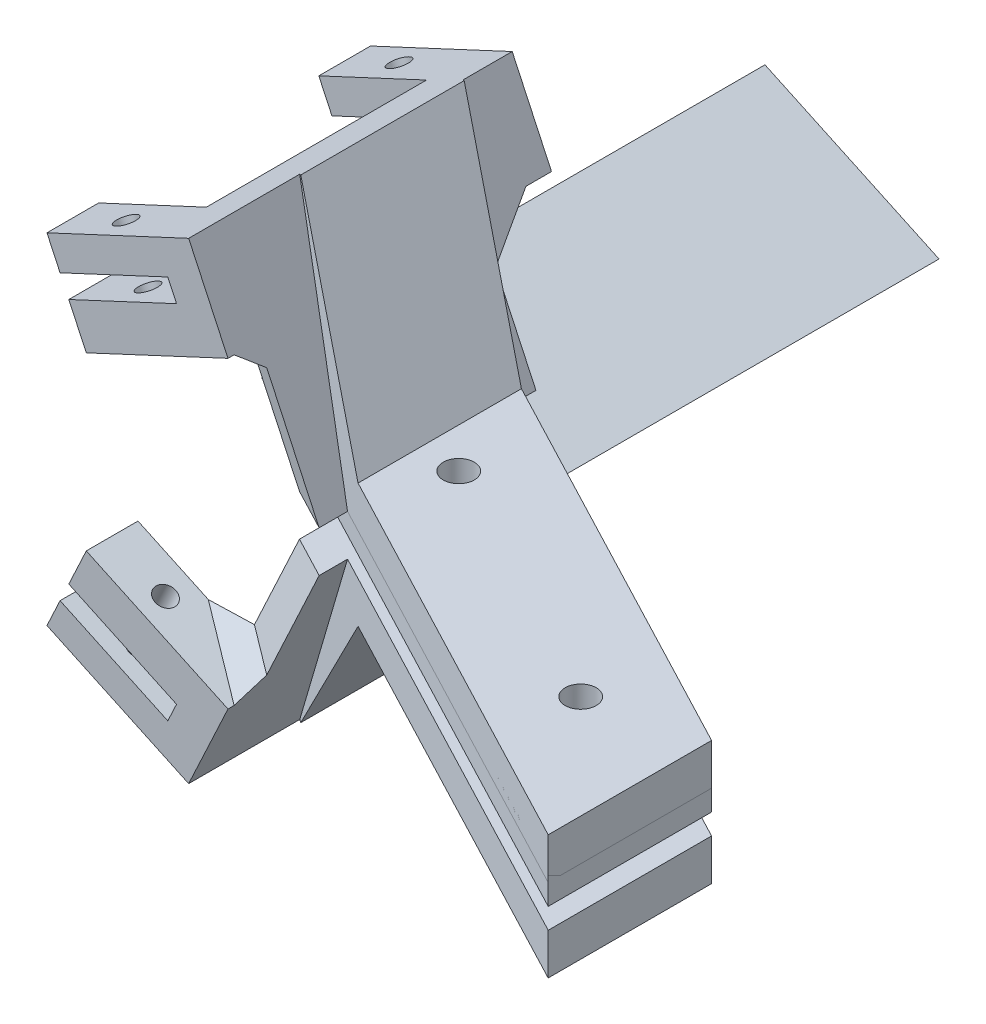
SolidWorks part; units mm, degrees
ref_plane "Front Plane" through (0, 0, 0) normal (0, 0, 1) x (1, 0, 0)
ref_plane "Top Plane" through (0, 0, 0) normal (0, 1, 0) x (1, 0, 0)
ref_plane "Right Plane" through (0, 0, 0) normal (1, 0, 0) x (0, 0, -1)
sketch "Sketch1" plane through (0, 0, 0) normal (0, 1, 0) x (1, 0, 0)
  line L0 (0, 6) -> (0, -19) construction
  line L1 (0, -19) -> (24.7992, -19) construction
  circle A0 centre (0, 0) radius 6
  circle A1 centre (24.7992, -13) radius 6
  dimension "D1" = 28
  dimension "D2" = 12
  dimension "D3" = 12
  dimension "D4" = 25
sketch "Sketch3" plane through (0, 0, 0) normal (0, 1, 0) x (1, 0, 0)
  line L0 (-10, 13.1456) -> (-10, -2.6614)
  line L1 (-10, -2.6614) -> (34.7992, -26.1456)
  line L2 (34.7992, -26.1456) -> (34.7992, -10.3386)
  line L3 (34.7992, -10.3386) -> (-10, 13.1456)
  line L5 (0, 0) -> (24.7992, -13) construction
  line L6 (0, 6) -> (0, -19) construction
  dimension "D1" = 7
  dimension "D2" = 7
  dimension "D3" = 10
  dimension "D4" = 10
extrude "Boss-Extrude1" add sketch "Sketch3" along normal blind 3
extrude "Boss-Extrude3" add sketch "Sketch1" against normal blind 2
sketch "Sketch4" plane through (0, 3, 0) normal (0, 1, 0) x (1, 0, 0)
  circle A0 centre (0, 0) radius 1.5
  circle A1 centre (24.7992, -13) radius 1.5
  dimension "D1" = 3
  dimension "D2" = 3
extrude "Cut-Extrude1" cut sketch "Sketch4" against normal through all
sketch "Sketch5" plane through (0, 3, 0) normal (0, 1, 0) x (1, 0, 0)
  circle A0 centre (0, 0) radius 3.25
  circle A1 centre (24.7992, -13) radius 3.25
  dimension "D1" = 6.5
  dimension "D2" = 6.5
extrude "Cut-Extrude2" cut sketch "Sketch5" against normal blind 2
sketch "Sketch6" plane through (0, -2, 0) normal (0, -1, 0) x (1, 0, 0)
  line L0 (-10, 2.6614) -> (-10, -13.1456)
  line L1 (-10, -13.1456) -> (34.7992, 10.3386)
  line L2 (34.7992, 10.3386) -> (34.7992, 26.1456)
  line L3 (34.7992, 26.1456) -> (-10, 2.6614)
  circle A0 centre (0, 0) radius 1.5
  circle A1 centre (24.7992, 13) radius 1.5
  circle A2 centre (24.7992, 13) radius 1.5 construction
  circle A3 centre (0, 0) radius 1.5 construction
extrude "Boss-Extrude4" add sketch "Sketch6" along normal blind 4 separate body
sketch "Sketch12" plane through (0, 0, 0) normal (0, 0, 1) x (1, 0, 0)
  line L0 (-10, -2) -> (-10, -18.3135)
  line L1 (-10, -18.3135) -> (-17.6071, -18.3135)
  line L2 (-17.6071, -18.3135) -> (-10, -2)
  line L3 (-10, -2) -> (-1.422, -6)
  line L4 (34.7992, -6) -> (-10, -6) construction
  dimension "D1" = 25
  dimension "D2" = 18
ref_plane "Plane1" through (0, -18.3135, 0) normal (0, -1, 0) x (-1, 0, 0)
sketch "Sketch7" plane through (0, -2, 0) normal (0, 1, 0) x (1, 0, 0)
  line L2 (-8, 14.8437) -> (-8, 12.0972) construction
  line L4 (-8, 12.0972) -> (-8, -3.7098) construction
  line L6 (-10, 15.8921) -> (-10, -5.4079)
  line L7 (-10, -5.4079) -> (-6, -7.5047)
  line L8 (-6, -7.5047) -> (-6, 13.7953)
  line L9 (-6, 13.7953) -> (-10, 15.8921)
  line L10 (-10, 13.1456) -> (34.7992, -10.3386) construction
  line L11 (-10, -2.6614) -> (-10, 13.1456) construction
  line L12 (34.7992, -26.1456) -> (-10, -2.6614) construction
  line L13 (-8, -3.7098) -> (-8, -6.4563) construction
  dimension "D1" = 21.3
  dimension "D2" = 4
sketch "Sketch16" plane through (0, -18.3135, 0) normal (0, -1, 0) x (-1, 0, 0)
  line L0 (13.6071, -7.5047) -> (13.6071, 13.7953)
  line L1 (13.6071, 13.7953) -> (17.6071, 15.8921)
  line L2 (17.6071, 15.8921) -> (17.6071, -5.4079)
  line L3 (17.6071, -5.4079) -> (13.6071, -7.5047)
  line L4 (6, 13.7953) -> (10, 15.8921) construction
  line L5 (10, 15.8921) -> (10, -5.4079) construction
  line L6 (10, -5.4079) -> (6, -7.5047) construction
loft "Loft1" add profiles "Sketch16", "Sketch7" connector at (-17.6071, -18.3135, 5.4079) connector at (-10, -2, 5.4079)
sketch "Sketch17" plane through (0, 0, 0) normal (0, 0, 1) x (1, 0, 0)
  line L0 (-17.6071, -18.3135) -> (-13.6071, -18.3135)
  line L1 (-13.6071, -18.3135) -> (-16.8927, -16.7815)
  line L2 (-17.6071, -18.3135) -> (-10, -2) construction
  line L3 (-16.8927, -16.7815) -> (-17.6071, -18.3135)
extrude "Cut-Extrude3" cut sketch "Sketch17" against normal through all both and the other way through all
sketch "Sketch9" plane through (-26.7054, -12.2057, 0) normal (0.4226, 0.9063, 0) x (-0.9063, 0.4226, 0)
  line L0 (-14.4524, 5.4079) -> (0.6729, 5.4079)
  line L2 (0.6729, 5.4079) -> (0.6729, 10.4079)
  line L3 (0.6729, 10.4079) -> (-14.4524, 10.4079)
  line L4 (-14.4524, 10.4079) -> (-14.4524, 5.4079)
  line L5 (-10.8271, -15.8921) -> (0.6729, -15.8921)
  line L6 (0.6729, -15.8921) -> (0.6729, -20.8921)
  line L7 (0.6729, -20.8921) -> (-14.4524, -20.8921)
  line L8 (-14.4524, -20.8921) -> (-14.4524, -15.8921)
  line L9 (-14.4524, -13.7953) -> (-10.8271, -15.8921)
  line L10 (-14.4524, -15.8921) -> (-14.4524, -13.7953)
  line L12 (-5.0771, 8.9579) -> (-5.0771, 10.4079) construction
  line L13 (-5.0771, -19.4421) -> (-5.0771, -20.8921) construction
  line L14 (-5.0771, 7.9579) -> (-5.0771, -18.4421) construction
  line L15 (-5.0771, -5.2421) -> (-10.8271, -5.2421) construction
  line L16 (-10.8271, -15.8921) -> (-10.8271, 5.4079) construction
  circle A0 centre (-5.0771, 7.9579) radius 1
  circle A1 centre (-5.0771, -18.4421) radius 1
  point P24 (-5.0771, -15.8921)
  dimension "D3" = 2
  dimension "D4" = 26.4
  dimension "D1" = 5
  dimension "D2" = 11.5
extrude "Boss-Extrude6" add sketch "Sketch9" along normal blind 4
sketch "Sketch10" plane through (-50.1145, -1.2899, 0) normal (0.4226, 0.9063, 0) x (-0.9063, 0.4226, 0)
  line L0 (-36.6562, 10.4079) -> (-36.6562, -20.8921)
  line L1 (-36.6562, -20.8921) -> (-40.2814, -20.8921)
  line L2 (-25.1562, -20.8921) -> (-40.2814, -20.8921) construction
  line L3 (-40.2814, -20.8921) -> (-40.2814, 10.4079)
  line L4 (-40.2814, 10.4079) -> (-25.1562, 10.4079) construction
  line L5 (-40.2814, 10.4079) -> (-36.6562, 10.4079)
  line L8 (-25.1562, 10.4079) -> (-40.2814, 10.4079) construction
  line L9 (-36.6562, -15.8921) -> (-36.6562, 5.4079) construction
extrude "Boss-Extrude7" add sketch "Sketch10" against normal blind 2
sketch "Sketch11" plane through (-10.29, -22.0671, 0) normal (-0.4226, -0.9063, 0) x (0.9063, -0.4226, 0)
  line L0 (-19.7178, 10.4079) -> (-4.5926, 10.4079)
  line L2 (-4.5926, 10.4079) -> (-4.5926, -20.8921)
  line L3 (-4.5926, -20.8921) -> (-19.7178, -20.8921)
  line L4 (-19.7178, -20.8921) -> (-19.7178, -15.8921)
  line L5 (-19.7178, -15.8921) -> (-8.2178, -15.8921)
  line L6 (-8.2178, -15.8921) -> (-8.2178, 5.4079)
  line L7 (-8.2178, 5.4079) -> (-19.7178, 5.4079)
  line L8 (-19.7178, 5.4079) -> (-19.7178, 10.4079)
  line L10 (-8.2178, -20.8921) -> (-8.2178, 10.4079) construction
  line L11 (-8.2178, -20.8921) -> (-8.2178, -15.8921) construction
  line L12 (-19.7178, -20.8921) -> (-19.7178, -15.8921) construction
  circle A0 centre (-13.9678, -18.4421) radius 1
  circle A1 centre (-13.9678, 7.9579) radius 1
  circle A2 centre (-13.9678, 7.9579) radius 1 construction
  circle A3 centre (-13.9678, -18.4421) radius 1 construction
extrude "Boss-Extrude8" add sketch "Sketch11" along normal blind 3
chamfer "Chamfer2" distance 4 angle 45 1 edges at (-13.5594, -13.9223, -14.8437)
chamfer "Chamfer3" distance 2 angle 45 1 edges at (-13.5594, -13.9223, 6.4563)
chamfer "Chamfer4" distance 20 distance2 4 1 edges at (-7.8652, -6, -4.123) first distance on face at (-10.3417, -11.3108, -3.8529)
mirror "Mirror1" about plane through (0, 0, 0) normal (0, 1, 0) of bodies 111
sketch "Sketch18" plane through (0, 0, 0) normal (0, 0, 1) x (1, 0, 0)
  line L0 (-10, 0) -> (-19.0631, 4.2262)
  line L1 (25.8707, 0) -> (-25.8707, 0) construction
  line L2 (-10, 3) -> (-10, 0) construction
  line L3 (-19.0631, 4.2262) -> (-17.3726, 7.8514)
  line L4 (-17.3726, 7.8514) -> (-0.5352, 0)
  line L5 (-0.5352, 0) -> (-10, 0)
  dimension "D1" = 4
  dimension "D2" = 25
  dimension "D3" = 10
extrude "Boss-Extrude9" add sketch "Sketch18" against normal blind 47 and the other way up to surface other way up to face at (12.3996, 1.5, 14.4035)
sketch "Sketch19" plane through (0, 1, 0) normal (0, 1, 0) x (1, 0, 0)
  circle A0 centre (0, 0) radius 3.25
  arc A1 (-2.6797, -1.8389) -> (-2.6797, 1.8389) centre (0, 0) ccw construction
extrude "Cut-Extrude4" cut sketch "Sketch19" along normal through all
sketch "Sketch20" plane through (0, 1, 0) normal (0, 1, 0) x (1, 0, 0)
  circle A0 centre (0, 0) radius 1.5
  circle A1 centre (0, 0) radius 1.5 construction
extrude "Cut-Extrude5" cut sketch "Sketch20" against normal through all
